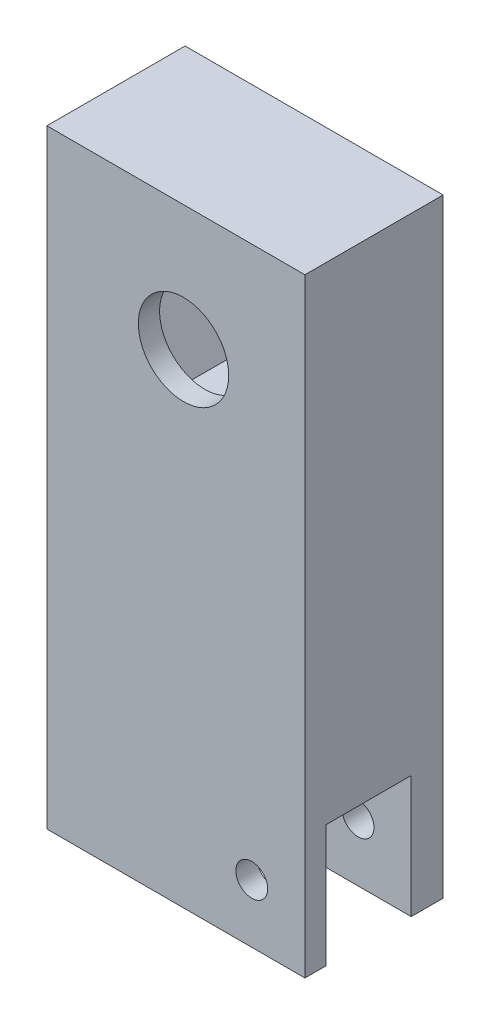
SolidWorks part; units mm, degrees
ref_plane "Front Plane" through (0, 0, 0) normal (0, 0, 1) x (1, 0, 0)
ref_plane "Top Plane" through (0, 0, 0) normal (0, 1, 0) x (1, 0, 0)
ref_plane "Right Plane" through (0, 0, 0) normal (1, 0, 0) x (0, 0, -1)
sketch "Sketch1" plane through (0, 0, 0) normal (0, 0, 1) x (1, 0, 0)
  line L0 (-449.5, -5.5) -> (-0.5, -5.5) construction
  line L1 (-57.5, -5.5) -> (-67.5, -5.5)
  line L2 (-57.5, -5.5) -> (-57.5, 5.5)
  line L3 (-57.5, 5.5) -> (-67.5, 5.5)
  line L4 (-67.5, -5.5) -> (-67.5, 5.5)
  line L5 (-0.5, 5.5) -> (-449.5, 5.5) construction
  line L6 (-449.5, 6) -> (-0.5, 6) construction
  line L7 (-60.7679, 3) -> (-64.2321, 3)
  line L8 (-64.2321, 3) -> (-65.9641, 0)
  line L9 (-65.9641, 0) -> (-64.2321, -3)
  line L10 (-64.2321, -3) -> (-60.7679, -3)
  line L11 (-60.7679, -3) -> (-59.0359, 0)
  line L12 (-59.0359, 0) -> (-60.7679, 3)
  line L13 (-64.9962, 33.1999) -> (-61.0702, 39.9999)
  line L14 (-61.0702, 39.9999) -> (-64.9962, 46.7999)
  line L15 (-64.9962, 46.7999) -> (-72.8482, 46.7999)
  line L16 (-72.8482, 46.7999) -> (-76.7742, 39.9999)
  line L17 (-76.7742, 39.9999) -> (-72.8482, 33.1999)
  line L18 (-72.8482, 33.1999) -> (-64.9962, 33.1999)
  line L19 (-81.7742, 51.7999) -> (-57.5, 51.7999)
  line L20 (-81.7742, 51.7999) -> (-81.7742, 5.5)
  line L21 (-81.7742, 5.5) -> (-57.5, 5.5)
  line L22 (-57.5, 51.7999) -> (-57.5, 5.5)
  line L23 (-81.7742, 5.5) -> (-67.5, 5.5)
  line L24 (-81.7742, 5.5) -> (-81.7742, -5.5)
  line L25 (-81.7742, -5.5) -> (-67.5, -5.5)
  line L26 (-67.5, 5.5) -> (-67.5, -5.5)
  line L27 (-81.7742, 6) -> (-56.6819, 6)
  line L28 (-81.7742, 6) -> (-81.7742, 8)
  line L29 (-81.7742, 8) -> (-56.6819, 8)
  line L30 (-56.6819, 6) -> (-56.6819, 8)
  circle A0 centre (-62.5, 0) radius 1.75 construction
  circle A1 centre (-62.5, 0) radius 3 construction
  circle A2 centre (-68.9222, 39.9999) radius 6.8 construction
  arc A3 (-69.0526, 43.4562) -> (-72.3763, 39.8216) centre (-68.9222, 39.9999) ccw construction
  circle A4 centre (-68.9222, 39.9999) radius 4.25
  circle A5 centre (-62.5, 0) radius 1.5
  dimension "D2" = 5
  dimension "D9" = 8.5
  dimension "D10" = 3
  dimension "D1" = 5
  dimension "D3" = 6
  dimension "D4" = 13.6
  dimension "D5" = 5
  dimension "D6" = 5
  dimension "D7" = 0
  dimension "D8" = 2
extrude "Boss-Extrude1" add sketch "Sketch1" along normal blind 2 contours L4 L1 L2 L3 L12 L11 L10 L9 L8 L7 | L24 L25 L4 L21 | L20 L29 L22 L19 L18 L17 L16 L15 L14 L13 | L29 L20 L27 L22 | L27 L20 L21 L3 L22 | L17 L18 L13 L14 L15 L16 | L11 L12 L7 L8 L9 L10 region at (-62.5, -5.3513, 0) region at (-74.6371, 0, 0) region at (-69.6371, 5.75, 0) region at (-69.6371, 7, 0) region at (-69.7639, 28.1084, 0) region at (-59.9813, 1.4542, 0) region at (-68.9222, 33.4077, 0)
extrude "Boss-Extrude2" add sketch "Sketch1<3>" against normal up to surface (8 mm away) contours L29 L20 L27 L22 | L20 L29 L22 L19 L18 L17 L16 L15 L14 L13 region at (-69.6371, 7, 0) region at (-69.7639, 28.1084, 0)
sketch "Sketch1<3>" plane through (0, 0, 0) normal (0, 0, 1) x (1, 0, 0) same geometry as "Sketch1"
extrude "Boss-Extrude3" add sketch "Sketch1<4>" against normal blind 3 from surface contours L20 L29 L22 L19 L18 L17 L16 L15 L14 L13 | L4 L1 L2 L3 L12 L11 L10 L9 L8 L7 | L27 L20 L21 L3 L22 | L29 L20 L27 L22 | L24 L25 L4 L21 | L11 L12 L7 L8 L9 L10 A5 region at (-62.5, -5.3513, 0) region at (-74.6371, 0, 0) region at (-69.6371, 5.75, 0) region at (-69.6371, 7, 0) region at (-69.7639, 28.1084, 0) region at (-59.9813, 1.4542, 0) starting at face at (-68.9222, 39.9999, -8)
sketch "Sketch1<4>" plane through (0, 0, 0) normal (0, 0, 1) x (1, 0, 0) same geometry as "Sketch1"
